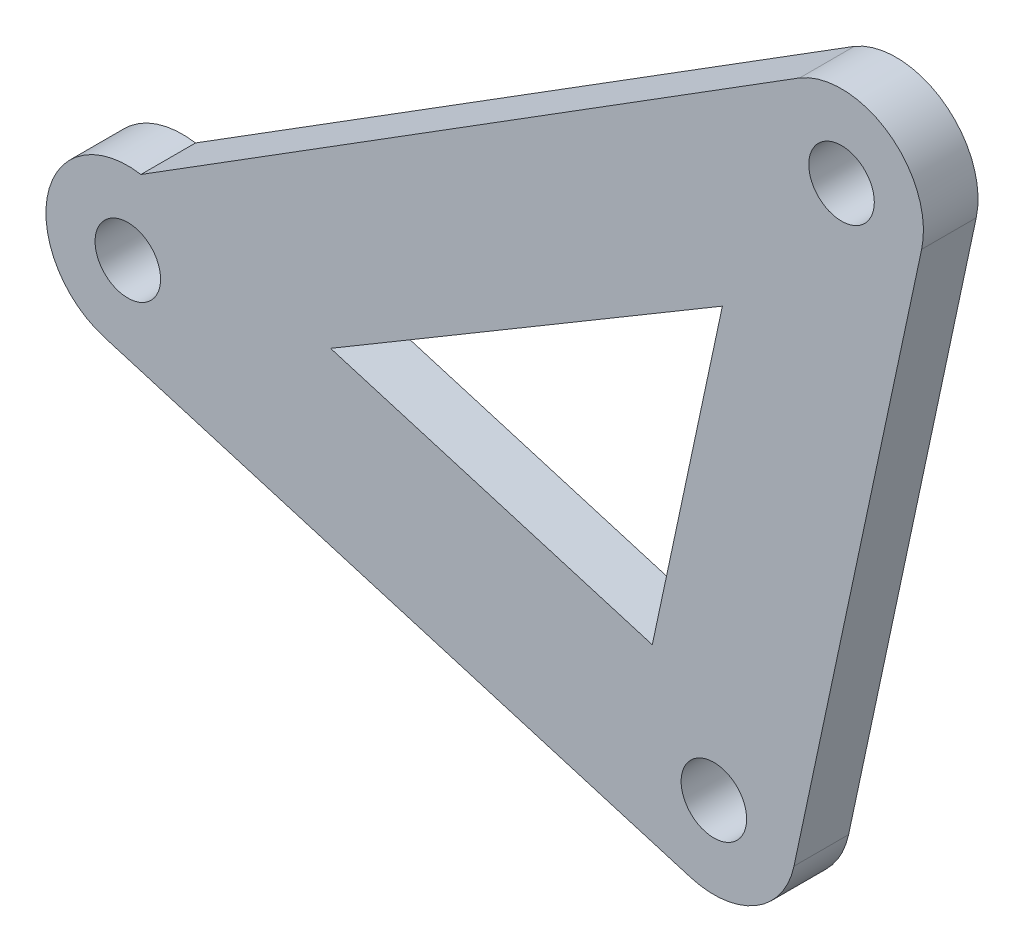
SolidWorks part; units mm, degrees
ref_plane "Plan de face" through (0, 0, 0) normal (0, 0, 1) x (1, 0, 0)
ref_plane "Plan de dessus" through (0, 0, 0) normal (0, 1, 0) x (1, 0, 0)
ref_plane "Plan de droite" through (0, 0, 0) normal (1, 0, 0) x (0, 0, -1)
sketch "Esquisse1" plane through (0, 0, 0) normal (0, 0, 1) x (1, 0, 0)
  line L0 (-117.6698, 11.9859) -> (-64, -4) construction
  line L1 (-115.5289, 19.1738) -> (-61.859, 3.1879)
  line L2 (-119.8108, 4.7979) -> (-66.141, -11.1879)
  line L3 (-64, -4) -> (-52.3085, 50.7659) construction
  line L4 (-71.3347, -2.4342) -> (-59.6432, 52.3318)
  line L5 (-56.6653, -5.5658) -> (-44.9738, 49.2001)
  line L6 (-52.3085, 50.7659) -> (-117.6698, 11.9859) construction
  line L7 (-48.4815, 44.3158) -> (-113.8429, 5.5357)
  line L8 (-56.1355, 57.2161) -> (-121.4968, 18.436)
  line L9 (-99.1029, 14.2812) -> (-63.2215, 35.5703)
  line L10 (-63.2215, 35.5703) -> (-69.6398, 5.5055)
  line L11 (-69.6398, 5.5055) -> (-99.1029, 14.2812)
  line L12 (-119.8108, 4.7979) -> (-66.141, -11.1879)
  line L13 (-44.9738, 49.2001) -> (-56.6653, -5.5658)
  line L14 (-56.1355, 57.2161) -> (-122.5274, 15.591)
  arc A0 (-115.5289, 19.1738) -> (-119.8108, 4.7979) centre (-117.6698, 11.9859) ccw
  arc A1 (-66.141, -11.1879) -> (-61.859, 3.1879) centre (-64, -4) ccw
  arc A2 (-71.3347, -2.4342) -> (-56.6653, -5.5658) centre (-64, -4) ccw
  arc A3 (-44.9738, 49.2001) -> (-59.6432, 52.3318) centre (-52.3085, 50.7659) ccw
  arc A4 (-48.4815, 44.3158) -> (-56.1355, 57.2161) centre (-52.3085, 50.7659) ccw
  arc A5 (-121.4968, 18.436) -> (-113.8429, 5.5357) centre (-117.6698, 11.9859) ccw
  point P4 (-90.8349, 3.9929)
  point P9 (-58.1543, 23.383)
  point P17 (-84.9892, 31.3759)
  point P24 (-63.2215, 35.5703)
  point P25 (-69.6398, 5.5055)
  point P26 (-99.1029, 14.2812)
  dimension "D1" = 15
  dimension "D2" = 15
  dimension "D3" = 15
extrude "Boss.-Extru.1" add sketch "Esquisse1" against normal blind 5 contours A3 L8 A0 L1 L7 L4 | L7 A4 A3 L4 | A4 L7 L4 L1 A1 L5 | L4 A2 A1 L1 | A5 L2 A2 L4 L1 L7 | A0 A5 L7 L1 region at (-84.2927, 31.9263, 0) region at (-114.889, 12.3296, 0) region at (-89.6282, 3.0064, 0) region at (-57.8667, 21.8511, 0) region at (-64.323, -3.4556, 0) region at (-53.943, 48.49, 0)
sketch "Esquisse2" plane through (0, 0, 0) normal (0, 0, 1) x (1, 0, 0)
  circle A0 centre (-117.6698, 11.9859) radius 3
  circle A1 centre (-64, -4) radius 3
  circle A2 centre (-52.3085, 50.7659) radius 3
  dimension "D1" = 6
  dimension "D2" = 6
  dimension "D3" = 6
extrude "Enlèv. mat.-Extru.1" cut sketch "Esquisse2" against normal through all both contours A0 | A1 | A2
